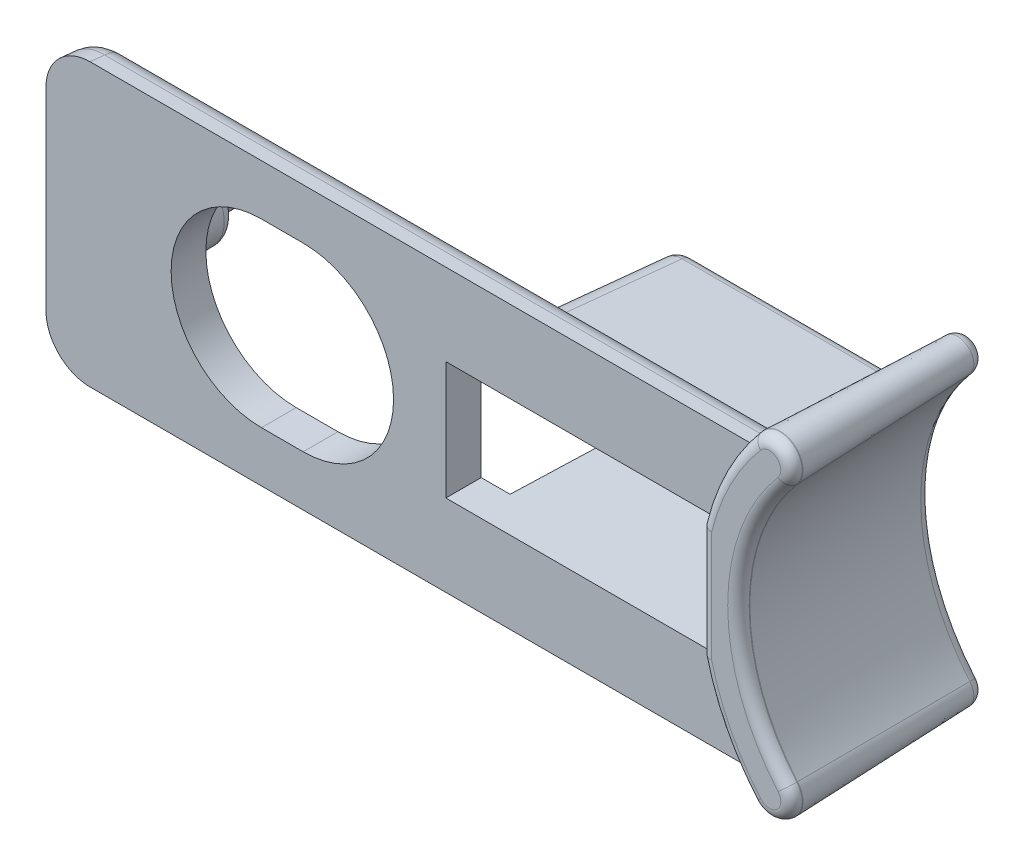
SolidWorks part; units mm, degrees
ref_plane "Front Plane" through (0, 0, 0) normal (0, 0, 1) x (1, 0, 0)
ref_plane "Top Plane" through (0, 0, 0) normal (0, 1, 0) x (1, 0, 0)
ref_plane "Right Plane" through (0, 0, 0) normal (1, 0, 0) x (0, 0, -1)
sketch "Sketch1" plane through (0, 0, 0) normal (0, 0, 1) x (1, 0, 0)
  line L1 (25.25, -7.9365) -> (-25.25, -7.9365)
  line L2 (25.25, -7.9365) -> (25.25, 7.9365)
  line L3 (25.25, 7.9365) -> (-25.25, 7.9365)
  line L4 (-25.25, -7.9365) -> (-25.25, 7.9365)
  line L5 (25.25, -7.9365) -> (-25.25, 7.9365) construction
  line L6 (25.25, 7.9365) -> (-25.25, -7.9365) construction
  point P0 (0, 0)
  dimension "D1" = 50.5
  dimension "D2" = 15.873
extrude "Boss-Extrude1" add sketch "Sketch1" along normal blind 2.5 draft 3 draft outward yes
sketch "Sketch2" plane through (0, 0, 0) normal (0, 0, -1) x (-1, 0, 0)
  line L0 (25.25, 7.9365) -> (25.25, -7.9365) construction
  circle A0 centre (20.25, 0) radius 1.585 construction
  circle A1 centre (20.25, 0) radius 5 construction
  circle A2 centre (20.25, 0) radius 2.75
  dimension "D1" = 3.17
  dimension "D2" = 10
  dimension "D3" = 5.5
extrude "Boss-Extrude2" add sketch "Sketch2" along normal blind 3.259 draft 1
sketch "Sketch3" plane through (0, 0, -3.259) normal (0, 0, -1) x (-1, 0, 0)
  circle A0 centre (20.25, 0) radius 1.585
  dimension "D1" = 3.17
extrude "Boss-Extrude3" add sketch "Sketch3" along normal blind 4
sketch "Sketch4" plane through (0, 0, 2.5) normal (0, 0, 1) x (1, 0, 0)
  line L0 (-9.881, 0) -> (-6.881, 0) construction
  line L1 (-9.881, 6.5) -> (-6.881, 6.5)
  line L2 (-9.881, -6.5) -> (-6.881, -6.5)
  line L4 (-25.381, 8.0675) -> (-25.381, -8.0675) construction
  arc A1 (-9.881, 6.5) -> (-9.881, -6.5) centre (-9.881, 0) ccw
  arc A4 (-6.881, -6.5) -> (-6.881, 6.5) centre (-6.881, 0) ccw
  point P0 (-8.381, 0)
  dimension "D3" = 6.5
  dimension "D2" = 3
  dimension "D1" = 15.5
extrude "Cut-Extrude1" cut sketch "Sketch4" against normal blind 4
sketch "Sketch9" plane through (0, 0, 0) normal (0, 0, -1) x (-1, 0, 0)
  line L1 (-5.5, 6.9365) -> (-25.25, 6.9365)
  line L2 (-5.5, 6.9365) -> (-5.5, -6.9365)
  line L3 (-5.5, -6.9365) -> (-25.25, -6.9365)
  line L4 (-25.25, 6.9365) -> (-25.25, -6.9365)
  line L5 (-25.25, -7.9365) -> (-25.25, 7.9365) construction
  line L6 (25.25, -7.9365) -> (-25.25, -7.9365) construction
  line L7 (-5.5, 0) -> (0, 0) construction
  dimension "D1" = 5.5
  dimension "D2" = 1
extrude "Boss-Extrude6" add sketch "Sketch9" along normal blind 11 draft 3
sketch "Sketch11" plane through (0, 0, 2.5) normal (0, 0, 1) x (1, 0, 0)
  line L0 (25.381, -8.0675) -> (25.381, 8.0675) construction
  line L1 (3.381, -4.25) -> (29.059, -4.25)
  line L2 (3.381, -4.25) -> (3.381, 4.25)
  line L3 (3.381, 4.25) -> (29.059, 4.25)
  line L4 (29.059, -4.25) -> (29.059, 4.25)
  line L5 (3.381, -4.25) -> (29.059, 4.25) construction
  line L6 (3.381, 4.25) -> (29.059, -4.25) construction
  point P0 (16.22, 0)
  dimension "D1" = 8.5
  dimension "D2" = 22
extrude "Cut-Extrude5" cut sketch "Sketch11" against normal offset from surface 2.5 draft 2 up to face at (15.375, 0, -11)
sketch "Sketch12" plane through (0, 0, -11) normal (0, 0, -1) x (-1, 0, 0)
  line L0 (-25.381, 8.0675) -> (25.381, 8.0675) construction
  line L1 (25.381, -8.0675) -> (-25.381, -8.0675) construction
  line L2 (-26.5858, 11.0675) -> (-28.3216, 9.5799) construction
  line L3 (-28.3216, -9.5799) -> (-26.5858, -11.0675) construction
  arc A0 (-26.5858, 11.0675) -> (-26.5858, -11.0675) centre (-39.5, 0) cw
  arc A1 (-28.3216, 9.5799) -> (-28.3216, -9.5799) centre (-39.5, 0) cw
  arc A2 (-26.5858, 11.0675) -> (-28.3216, 9.5799) centre (-27.4537, 10.3237) ccw
  arc A3 (-28.3216, -9.5799) -> (-26.5858, -11.0675) centre (-27.4537, -10.3237) ccw
  dimension "D1" = 3
  dimension "D2" = 3
  dimension "D4" = 39.5
  dimension "D3" = 2.286
extrude "Boss-Extrude7" add sketch "Sketch12" against normal up to vertex (13.5 mm away) draft 2 up to point (25.381, -8.0675, 2.5) draft outward yes
sketch "Sketch13" plane through (0, 0, 0) normal (0, 0, -1) x (-1, 0, 0)
  line L0 (25.25, 6.823) -> (25.25, 10)
  line L1 (25.25, 10) -> (-26.3139, 10)
  line L2 (-26.3139, 10) -> (-26.3139, 6.823)
  line L3 (-26.3139, 6.823) -> (25.25, 6.823)
  line L4 (0, 0) -> (-17.3627, 0) construction
  line L5 (-26.3139, -6.823) -> (25.25, -6.823)
  line L6 (-26.3139, -10) -> (-26.3139, -6.823)
  line L7 (25.25, -10) -> (-26.3139, -10)
  line L8 (25.25, -6.823) -> (25.25, -10)
  line L9 (25.25, 7.9365) -> (25.25, -7.9365) construction
  dimension "D1" = 10
extrude "Boss-Extrude8" add sketch "Sketch13" against normal up to vertex (2.5 mm away) draft 3 up to point (23.9939, 8.0675, 2.5) draft outward yes
fillet "Fillet2" radius 3.175 2 edges at (-25.3155, 10.0655, 1.25) (-25.3155, -10.0655, 1.25)
fillet "Fillet3" radius 1.5875 4 edges at (5.7882, 6.6483, -5.5) (5.7882, -6.6483, -5.5) (23.6372, -6.6475, -5.5152) (23.6372, 6.6475, -5.5152)
fillet "Fillet4" radius 0.7937 12 edges at (25.2278, -9.2504, -11) (28.1975, -11.1916, -11) (24.7782, 0, -11) (28.1975, 11.1916, -11) (25.2278, 9.2504, -11) (15.1758, 6.36, -11) (6.5406, 5.8959, -11) (6.0765, 0, -11) (6.5406, -5.8959, -11) (15.1758, -6.36, -11) (23.3854, -6.5208, -11) (23.6801, 6.7074, -11)
fillet "Fillet5" radius 1.5875 5 edges at (1.5956, 10, 0) (-24.3219, 9.0719, 0) (-25.25, 0, 0) (-24.3219, -9.0719, 0) (1.5956, -10, 0)
sketch "Sketch18" plane through (0, 0, 2.5) normal (0, 0, 1) x (1, 0, 0)
  line L1 (20.8594, 6.2159) -> (23.8479, 6.2159)
  line L2 (20.8594, 6.2159) -> (20.8594, -6.0369)
  line L3 (20.8594, -6.0369) -> (23.8479, -6.0369)
  line L4 (23.8479, 6.2159) -> (23.8479, -6.0369)
extrude "Boss-Extrude10" add sketch "Sketch18" against normal up to vertex (11 mm away) up to point (22.8477, 3.8659, -8.5)
sketch "Sketch15" plane through (0, 0, 2.5) normal (0, 0, 1) x (1, 0, 0)
  line L1 (3.381, 4.25) -> (22.5, 4.25)
  line L2 (3.381, 4.25) -> (3.381, -4.25)
  line L3 (3.381, -4.25) -> (22.5, -4.25)
  line L4 (22.5, 4.25) -> (22.5, -4.25)
  dimension "D1" = 22.5
extrude "Cut-Extrude7" cut sketch "Sketch15" against normal up to vertex (11 mm away) draft 1 up to point (5.9455, 3.8659, -8.5)
fillet "Fillet6" radius 0.7937 2 edges at (-21.835, 0, -7.259) (-22.9431, 0, -3.259)
sketch "Sketch16" plane through (0, 0, 2.5) normal (0, 0, 1) x (1, 0, 0)
  line L0 (-22.631, 4) -> (-22.631, -4) construction
  line L1 (-21.131, 4) -> (-21.131, -4)
  line L2 (-24.131, 4) -> (-24.131, -4)
  line L4 (-25.381, 6.9604) -> (-25.381, -6.9604) construction
  arc A0 (-21.131, 4) -> (-24.131, 4) centre (-22.631, 4) ccw
  arc A1 (-24.131, -4) -> (-21.131, -4) centre (-22.631, -4) ccw
  point P2 (-22.631, 0)
  dimension "D1" = 1.25
  dimension "D2" = 3
  dimension "D3" = 8
extrude "Boss-Extrude9" [suppressed] add sketch "Sketch16" along normal blind 2.5
fillet "Fillet7" [suppressed] radius 1
sketch "Sketch19" plane through (0, 0, 2.5) normal (0, 0, 1) x (1, 0, 0)
  line L0 (22.5, 4.065) -> (22.5, -4.065)
  arc A0 (28.6796, 9.2732) -> (28.6796, -9.2732) centre (39.5, 0) ccw construction
  arc A1 (28.6796, 9.2732) -> (26.2279, 11.3743) centre (27.4537, 10.3237) ccw construction
  arc A2 (26.2279, 11.3743) -> (25.2562, 10.131) centre (39.5, 0) ccw construction
  arc A3 (26.2279, -11.3743) -> (28.6796, -9.2732) centre (27.4537, -10.3237) ccw construction
  arc A4 (25.2562, -10.131) -> (26.2279, -11.3743) centre (39.5, 0) ccw construction
  arc A5 (28.6796, 9.2732) -> (28.6796, -9.2732) centre (39.5, 0) ccw
  arc A6 (28.6796, 9.2732) -> (26.2279, 11.3743) centre (27.4537, 10.3237) ccw
  arc A7 (26.2279, 11.3743) -> (22.5, 4.065) centre (39.5, 0) ccw
  arc A8 (26.2279, -11.3743) -> (28.6796, -9.2732) centre (27.4537, -10.3237) ccw
  arc A9 (25.2562, -10.131) -> (26.2279, -11.3743) centre (39.5, 0) ccw
  arc A10 (22.5, -4.065) -> (25.2562, -10.131) centre (39.5, 0) ccw
extrude "Boss-Extrude11" add sketch "Sketch19" along normal blind 0.8 draft 3
fillet "Fillet8" radius 0.7937 6 edges at (28.477, 11.5177, 3.3) (25.2077, 0, 3.3) (28.477, -11.5177, 3.3) (23.9674, -7.9246, 3.3) (23.9674, 7.9246, 3.3) (22.5419, 0, 3.3)
